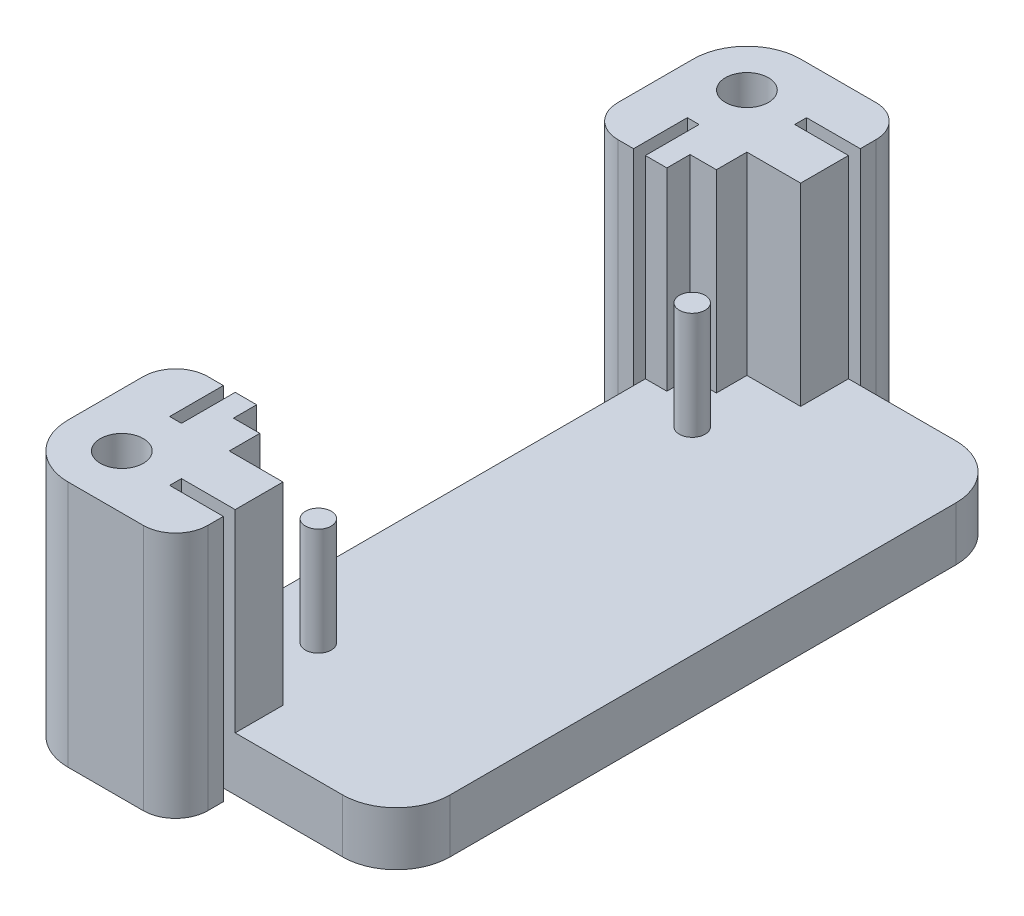
SolidWorks part; units mm, degrees
ref_plane "Front Plane" through (0, 0, 0) normal (0, 0, 1) x (1, 0, 0)
ref_plane "Top Plane" through (0, 0, 0) normal (0, 1, 0) x (1, 0, 0)
ref_plane "Right Plane" through (0, 0, 0) normal (1, 0, 0) x (0, 0, -1)
sketch "Sketch1" plane through (0, 0, 0) normal (0, 1, 0) x (1, 0, 0)
  line L0 (-36.79, 24.09) -> (36.79, 24.09)
  line L1 (-46.79, -34.09) -> (46.79, -34.09)
  line L2 (-46.79, -34.09) -> (-46.79, 34.09)
  line L3 (-46.79, 34.09) -> (46.79, 34.09)
  line L4 (46.79, -34.09) -> (46.79, 34.09)
  line L5 (-46.79, -34.09) -> (46.79, 34.09) construction
  line L6 (-46.79, 34.09) -> (46.79, -34.09) construction
  line L7 (36.79, -24.09) -> (36.79, 24.09)
  line L8 (-36.79, -24.09) -> (36.79, -24.09)
  line L9 (-36.79, -24.09) -> (-36.79, 24.09)
  line L10 (-31.79, 34.09) -> (-31.79, 24.09)
  line L11 (-46.79, 19.09) -> (-36.79, 19.09)
  line L12 (0, 34.09) -> (0, -34.09) construction
  line L13 (-46.79, 0) -> (46.79, 0) construction
  line L14 (-36.79, 24.09) -> (-46.79, 24.09)
  line L15 (-36.79, 24.09) -> (-36.79, 34.09)
  line L16 (-41.79, 34.09) -> (-41.79, -34.09) construction
  line L17 (-46.79, 29.09) -> (46.79, 29.09) construction
  line L18 (42.34, 34.09) -> (42.34, -34.09)
  line L19 (-42.34, 34.09) -> (-41.24, 34.09)
  line L20 (-42.34, 34.09) -> (-42.34, -34.09)
  line L21 (-42.34, -34.09) -> (-41.24, -34.09)
  line L22 (-41.24, 34.09) -> (-41.24, -34.09)
  line L23 (-46.79, 29.64) -> (46.79, 29.64)
  line L24 (-46.79, 29.64) -> (-46.79, 28.54)
  line L25 (-46.79, 28.54) -> (46.79, 28.54)
  line L26 (46.79, 29.64) -> (46.79, 28.54)
  line L27 (41.24, 34.09) -> (41.24, -34.09)
  line L28 (31.79, 34.09) -> (31.79, 24.09)
  line L29 (46.79, 19.09) -> (36.79, 19.09)
  line L30 (36.79, 24.09) -> (46.79, 24.09)
  line L31 (36.79, 24.09) -> (36.79, 34.09)
  line L32 (-31.79, -34.09) -> (-31.79, -24.09)
  line L33 (-36.79, -24.09) -> (-36.79, -34.09)
  line L34 (-36.79, -24.09) -> (-46.79, -24.09)
  line L35 (-46.79, -19.09) -> (-36.79, -19.09)
  line L36 (46.79, -19.09) -> (36.79, -19.09)
  line L37 (36.79, -24.09) -> (46.79, -24.09)
  line L38 (36.79, -24.09) -> (36.79, -34.09)
  line L39 (31.79, -34.09) -> (31.79, -24.09)
  line L40 (-46.79, -28.54) -> (46.79, -28.54)
  line L41 (-46.79, -29.64) -> (46.79, -29.64)
  point P0 (0, 0)
  point P22 (-41.79, 19.09)
  point P25 (-36.79, 29.09)
  point P30 (-41.79, -34.09)
  point P35 (46.79, 29.09)
  dimension "D1" = 93.58
  dimension "D2" = 68.18
  dimension "D4" = 15
  dimension "D5" = 15
  dimension "D6" = 1.1
  dimension "D7" = 1.1
  dimension "D3" = 10
extrude "Base" add sketch "Sketch1" along normal blind 5 contours L1 L4 L3 L2
extrude "Walls" add sketch "Sketch1<3>" along normal blind 23 contours L2 L23 L20 L3 | L22 L23 L15 L3 | L25 L22 L14 L15 | L25 L2 L14 L20 | L20 L23 L22 L3 | L22 L25 L15 L23 | L2 L25 L20 L23 | L25 L20 L14 L22 | L20 L25 L22 L23 | L14 L22 L11 L9 | L20 L14 L2 L11 | L25 L15 L0 L10 | L15 L23 L10 L3 | L35 L2 L34 L20 | L35 L22 L34 L9 | L22 L40 L33 L34 | L2 L40 L20 L34 | L41 L2 L1 L20 | L41 L22 L1 L33 | L41 L33 L1 L32 | L33 L40 L32 L8 | L22 L41 L33 L40 | L2 L41 L20 L40 | L41 L20 L1 L22 | L20 L41 L22 L40 | L20 L40 L22 L34 | L41 L39 L1 L38 | L39 L40 L38 L8 | L38 L40 L27 L37 | L41 L38 L1 L27 | L41 L18 L1 L4 | L18 L40 L4 L37 | L7 L37 L27 L36 | L18 L37 L4 L36 | L27 L40 L18 L37 | L27 L41 L18 L40 | L41 L27 L1 L18 | L38 L41 L27 L40 | L18 L41 L4 L40 | L30 L18 L29 L4 | L0 L31 L25 L28 | L30 L7 L29 L27 | L23 L31 L3 L28 | L31 L30 L27 L25 | L31 L23 L27 L3 | L18 L23 L4 L3 | L18 L30 L4 L25 | L27 L30 L18 L25 | L3 L27 L23 L18 | L31 L25 L27 L23 | L23 L27 L25 L18 | L18 L25 L4 L23 | L22 L14 L20 L11 | L15 L25 L10 L23 | L35 L20 L34 L22 | L33 L41 L32 L40 | L39 L41 L38 L40 | L27 L37 L18 L36 | L30 L27 L29 L18 | L25 L31 L23 L28 region at (-34.29, 0, -26.315) region at (-39.015, 0, -21.59) region at (-39.015, 0, -26.315) region at (-41.79, 0, -21.59) region at (-41.79, 0, -26.315) region at (-39.015, 0, -29.09) region at (-34.29, 0, -29.09) region at (34.29, 0, -26.315) region at (-39.015, 0, 21.59) region at (-44.565, 0, -21.59) region at (-44.565, 0, -26.315) region at (-41.79, 0, -29.09) region at (-39.015, 0, -31.865) region at (-34.29, 0, -31.865) region at (39.015, 0, -21.59) region at (39.015, 0, -26.315) region at (34.29, 0, -29.09) region at (-34.29, 0, 26.315) region at (-39.015, 0, 26.315) region at (-41.79, 0, 21.59) region at (-44.565, 0, -29.09) region at (-41.79, 0, -31.865) region at (41.79, 0, -21.59) region at (41.79, 0, -26.315) region at (39.015, 0, -29.09) region at (34.29, 0, -31.865) region at (-34.29, 0, 29.09) region at (-39.015, 0, 29.09) region at (-41.79, 0, 26.315) region at (-44.565, 0, 21.59) region at (-44.565, 0, -31.865) region at (39.015, 0, 21.59) region at (41.79, 0, -29.09) region at (44.565, 0, -21.59) region at (44.565, 0, -26.315) region at (39.015, 0, -31.865) region at (34.29, 0, 26.315) region at (-34.29, 0, 31.865) region at (-39.015, 0, 31.865) region at (-41.79, 0, 29.09) region at (-44.565, 0, 26.315) region at (39.015, 0, 26.315) region at (41.79, 0, 21.59) region at (44.565, 0, -29.09) region at (41.79, 0, -31.865) region at (34.29, 0, 29.09) region at (-41.79, 0, 31.865) region at (-44.565, 0, 29.09) region at (41.79, 0, 26.315) region at (39.015, 0, 29.09) region at (44.565, 0, 21.59) region at (44.565, 0, -31.865) region at (34.29, 0, 31.865) region at (-44.565, 0, 31.865) region at (41.79, 0, 29.09) region at (44.565, 0, 26.315) region at (39.015, 0, 31.865) region at (41.79, 0, 31.865) region at (44.565, 0, 29.09) region at (44.565, 0, 31.865)
sketch "Sketch1<3>" plane through (0, 0, 0) normal (0, 1, 0) x (1, 0, 0) same geometry as "Sketch1"
extrude "Acrylic Cut" cut sketch "Sketch1<4>" along normal up to surface (23 mm away) contours L32 L41 L39 L40 | L33 L41 L32 L40 | L39 L41 L38 L40 | L35 L20 L34 L22 | L20 L35 L22 L11 | L22 L14 L20 L11 | L28 L23 L10 L25 | L15 L25 L10 L23 | L25 L31 L23 L28 | L30 L27 L29 L18 | L36 L18 L29 L27 | L27 L37 L18 L36 region at (-41.79, 0, -21.59) region at (-34.29, 0, -29.09) region at (0, 0, -29.09) region at (-41.79, 0, 0) region at (34.29, 0, -29.09) region at (-41.79, 0, 21.59) region at (41.79, 0, -21.59) region at (-34.29, 0, 29.09) region at (41.79, 0, 0) region at (0, 0, 29.09) region at (41.79, 0, 21.59) region at (34.29, 0, 29.09) up to face at (38.4567, 23, 25.7567)
sketch "Sketch1<4>" plane through (0, 0, 0) normal (0, 1, 0) x (1, 0, 0) same geometry as "Sketch1"
sketch "Sketch2" plane through (0, 23, 0) normal (0, 1, 0) x (1, 0, 0)
  line L1 (-46.79, 19.09) -> (-42.34, 19.09)
  line L2 (-46.79, 19.09) -> (-46.79, -19.09)
  line L3 (-46.79, -19.09) -> (-42.34, -19.09)
  line L4 (-42.34, 19.09) -> (-42.34, -19.09)
  line L5 (-31.79, 34.09) -> (31.79, 34.09)
  line L6 (-31.79, 34.09) -> (-31.79, 29.64)
  line L7 (-31.79, 29.64) -> (31.79, 29.64)
  line L8 (31.79, 34.09) -> (31.79, 29.64)
  line L9 (46.79, 19.09) -> (42.34, 19.09)
  line L10 (46.79, 19.09) -> (46.79, -19.09)
  line L11 (46.79, -19.09) -> (42.34, -19.09)
  line L12 (42.34, 19.09) -> (42.34, -19.09)
  line L13 (31.79, -34.09) -> (-31.79, -34.09)
  line L14 (31.79, -34.09) -> (31.79, -29.64)
  line L15 (31.79, -29.64) -> (-31.79, -29.64)
  line L16 (-31.79, -34.09) -> (-31.79, -29.64)
extrude "Cut-Extrude2" cut sketch "Sketch2" against normal through all
sketch "Sketch3" plane through (0, 5, 0) normal (0, 1, 0) x (1, 0, 0)
  line L0 (41.24, 0) -> (-41.24, 0) construction
  line L1 (41.24, 19.09) -> (41.24, -19.09) construction
  line L2 (-41.24, 19.09) -> (-41.24, -19.09) construction
  line L3 (0, -28.54) -> (0, 28.54) construction
  line L4 (-31.79, -28.54) -> (31.79, -28.54) construction
  line L5 (-31.79, 28.54) -> (31.79, 28.54) construction
  line L7 (18.76, 21.25) -> (-39.24, 21.25)
  line L8 (18.76, 21.25) -> (18.76, -21.25)
  line L9 (18.76, -21.25) -> (-39.24, -21.25)
  line L10 (-39.24, 21.25) -> (-39.24, -21.25)
  circle A0 centre (14.71, 17.4) radius 1.4
  circle A1 centre (-35.19, 17.4) radius 1.4
  circle A2 centre (-35.19, -17.4) radius 1.4
  circle A3 centre (14.71, -17.4) radius 1.4
  circle A4 centre (-35.19, -17.4) radius 1.2
  circle A5 centre (14.71, -17.4) radius 1.2
  circle A6 centre (14.71, 17.4) radius 1.2
  circle A7 centre (-35.19, 17.4) radius 1.2
  dimension "D5" = 2.8
  dimension "D6" = 2.8
  dimension "D7" = 4.05
  dimension "D8" = 3.85
  dimension "D9" = 4.05
  dimension "D10" = 3.85
  dimension "D1" = 42.5
  dimension "D2" = 58
  dimension "D3" = 21.25
  dimension "D4" = 18.76
  dimension "D11" = 0.2
extrude "Board Cutout" cut sketch "Sketch3" along normal up to surface (18 mm away) contours L10 L9 L8 L7 up to face at (-38.2186, 23, 25.5186)
extrude "Screw Holes" add sketch "Sketch3<2>" along normal blind 10 contours A4 | A5 | A6 | A7
sketch "Sketch3<2>" plane through (0, 5, 0) normal (0, 1, 0) x (1, 0, 0) same geometry as "Sketch3"
fillet "Fillet1" radius 5 4 edges at (46.79, 11.5, -34.09) (-46.79, 11.5, -34.09) (46.79, 11.5, 34.09) (-46.79, 11.5, 34.09)
fillet "Fillet3" radius 3 8 edges at (-46.79, 11.5, 19.09) (-46.79, 11.5, -19.09) (-31.79, 11.5, -34.09) (31.79, 11.5, -34.09) (46.79, 11.5, 19.09) (46.79, 11.5, -19.09) (31.79, 11.5, 34.09) (-31.79, 11.5, 34.09)
sketch "Sketch5" plane through (0, 5, 0) normal (0, 1, 0) x (1, 0, 0)
  line L0 (46.79, -29.09) -> (46.79, -22.09) construction
  line L1 (46.79, -34.09) -> (-16.79, -34.09)
  line L2 (46.79, -34.09) -> (46.79, 34.09)
  line L3 (46.79, 34.09) -> (-16.79, 34.09)
  line L4 (-16.79, -34.09) -> (-16.79, 34.09)
  line L5 (34.79, -34.09) -> (41.79, -34.09) construction
  line L6 (34.79, 34.09) -> (41.79, 34.09) construction
  line L8 (-36.79, -24.09) -> (-36.79, -21.25) construction
  dimension "D1" = 20
sketch "Sketch4" plane through (0, 5, 0) normal (0, 1, 0) x (1, 0, 0)
  line L0 (-46.79, -29.09) -> (-46.79, -22.09) construction
  line L1 (-46.79, -34.09) -> (3.21, -34.09)
  line L2 (-46.79, -34.09) -> (-46.79, 34.09)
  line L3 (-46.79, 34.09) -> (3.21, 34.09)
  line L4 (3.21, -34.09) -> (3.21, 34.09)
  line L5 (-41.79, -34.09) -> (-34.79, -34.09) construction
  line L6 (-41.79, 34.09) -> (-34.79, 34.09) construction
  dimension "D1" = 50
sketch "Sketch6" plane through (0, 23, 0) normal (0, 1, 0) x (1, 0, 0)
  line L0 (-41.79, 34.09) -> (-41.79, 24.09) construction
  line L1 (-46.79, 29.09) -> (-36.79, 29.09) construction
  line L2 (-46.79, 22.09) -> (-46.79, 29.09) construction
  line L3 (-41.79, 34.09) -> (-34.79, 34.09) construction
  line L4 (-36.79, 28.54) -> (-36.79, 29.64) construction
  line L5 (-41.24, 24.09) -> (-42.34, 24.09) construction
  line L6 (0, 28.54) -> (0, -28.54) construction
  line L7 (-31.79, 28.54) -> (31.79, 28.54) construction
  line L8 (-31.79, -28.54) -> (31.79, -28.54) construction
  line L9 (-41.24, 0) -> (41.24, 0) construction
  line L10 (-41.24, 19.09) -> (-41.24, -19.09) construction
  line L11 (41.24, 19.09) -> (41.24, -19.09) construction
  circle A0 centre (-41.79, 29.09) radius 2
  circle A1 centre (41.79, 29.09) radius 2
  circle A2 centre (41.79, -29.09) radius 2
  circle A3 centre (-41.79, -29.09) radius 2
  dimension "D3" = 4
  dimension "D1" = 5
  dimension "D2" = 5
extrude "Cut-Extrude3" cut sketch "Sketch6" against normal through all
extrude "Bottom Half Cut" cut sketch "Sketch5" against normal through all both and the other way through all
fillet "Fillet4" radius 5 2 edges at (-16.79, 2.5, -28.54) (-16.79, 2.5, 28.54)
extrude "Top Half Cut" [suppressed] cut sketch "Sketch4" against normal through all both and the other way through all
fillet "Fillet5" [suppressed] radius 5
equation "\"acrylic_thickness\"= 1mm"
equation "\"D6@Sketch1\"=\"acrylic_thickness\"*1.1"
equation "\"D7@Sketch1\"=\"acrylic_thickness\"*1.1"
equation "\"wall_thickness\"= 10mm"
equation "\"D3@Sketch1\"=\"wall_thickness\""
